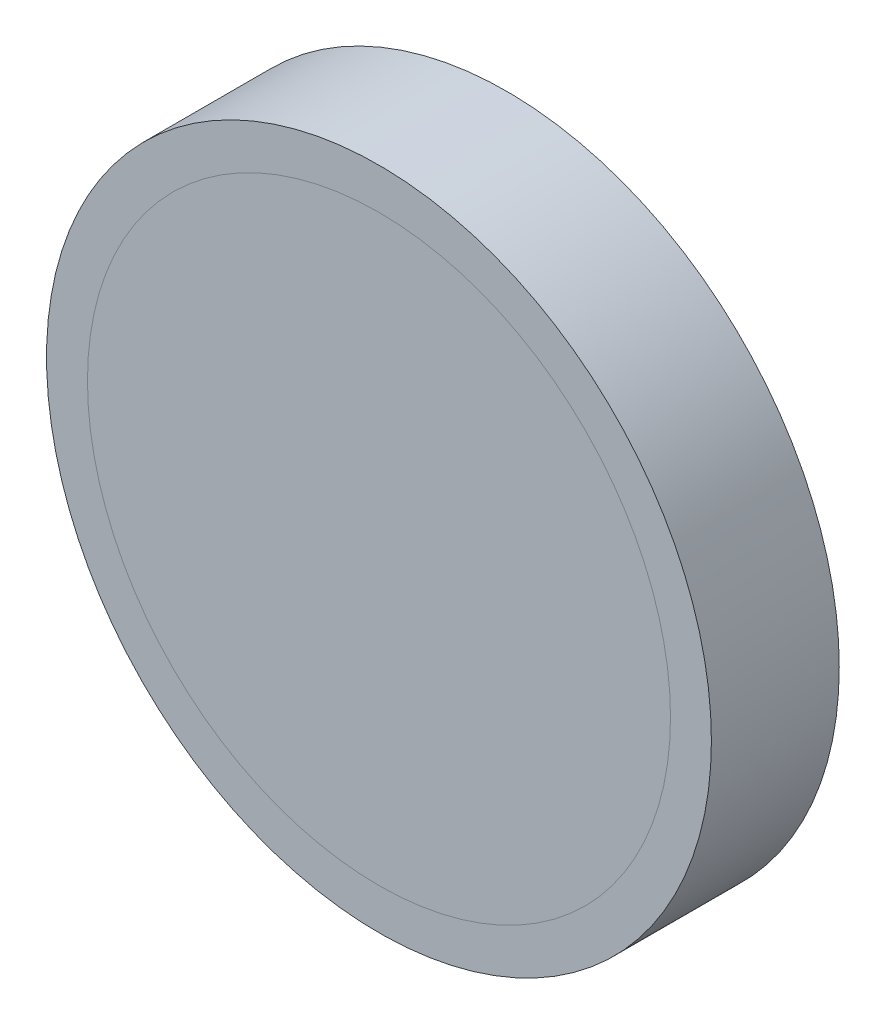
SolidWorks part; units mm, degrees
material "Nylon 101"
ref_plane "Front Plane" through (0, 0, 0) normal (0, 0, 1) x (1, 0, 0)
ref_plane "Top Plane" through (0, 0, 0) normal (0, 1, 0) x (1, 0, 0)
ref_plane "Right Plane" through (0, 0, 0) normal (1, 0, 0) x (0, 0, -1)
sketch "Sketch1" plane through (0, 0, 0) normal (0, 0, 1) x (1, 0, 0)
  circle A1 centre (-6.731, -165.7192) radius 4.1275
  circle A2 centre (-6.731, -165.7192) radius 4.1275
  dimension "D1" = 0
extrude "Boss-Extrude1" add sketch "Sketch1" along normal blind 1.5875
sketch "Sketch2" plane through (0, 0, 1.5875) normal (0, 0, 1) x (1, 0, 0)
  circle A0 centre (-6.731, -165.7192) radius 3.6195
  circle A1 centre (-6.731, -165.7192) radius 4.1275
  circle A2 centre (-6.731, -165.7192) radius 4.1275
  dimension "D1" = 0
  dimension "D2" = 0.508
wrap "Wrap1" sketch "Sketch2" wrap type scribe source sketch "Sketch2" face at (-2.6035, -165.7192, 1.5875)
